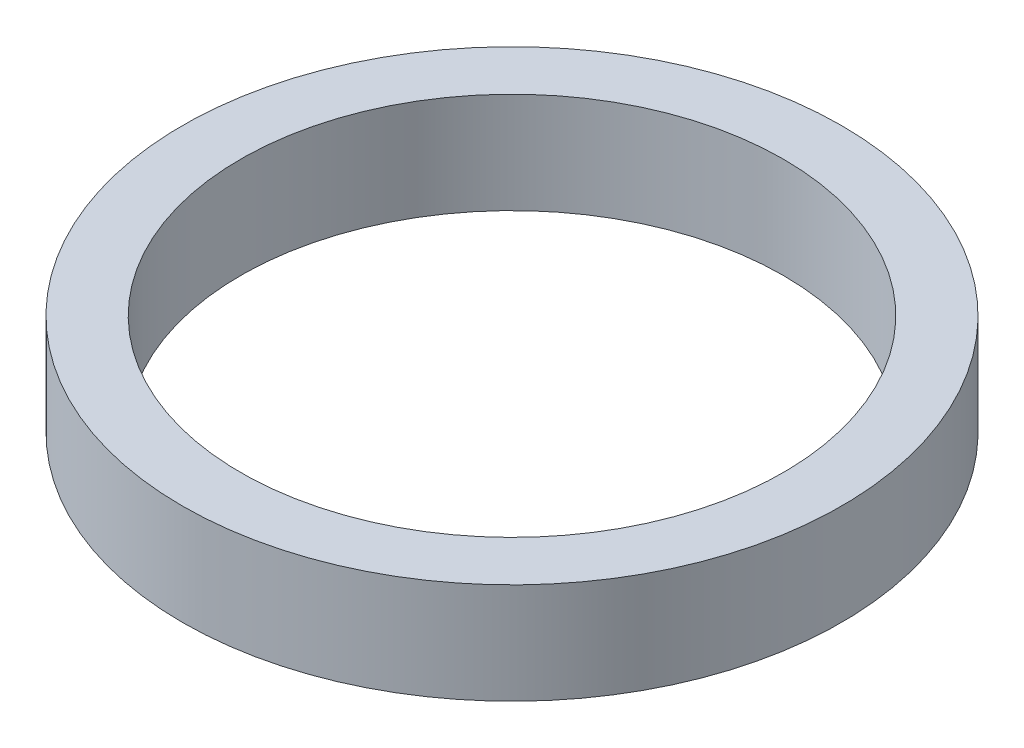
SolidWorks part; units mm, degrees
ref_plane "Front Plane" through (0, 0, 0) normal (0, 0, 1) x (1, 0, 0)
ref_plane "Top Plane" through (0, 0, 0) normal (0, 1, 0) x (1, 0, 0)
ref_plane "Right Plane" through (0, 0, 0) normal (1, 0, 0) x (0, 0, -1)
sketch "Sketch1" plane through (0, 0, 0) normal (0, 1, 0) x (1, 0, 0)
  circle A0 centre (0, 0) radius 42.5
  dimension "FLANGE_OD" = 85
extrude "Boss-Extrude1" add sketch "Sketch1" along normal blind 13
sketch "Sketch2" plane through (0, 0, 0) normal (0, 1, 0) x (1, 0, 0)
  circle A0 centre (0, 0) radius 35
  dimension "BORE_D" = 70
extrude "Cut-Extrude1" cut sketch "Sketch2" along normal through all
sketch "Sketch3" plane through (0, 13, 0) normal (0, 1, 0) x (1, 0, 0)
  circle A0 centre (0, 0) radius 19.6855 construction
  circle A1 centre (-19.6855, 0) radius 1.5
  dimension "BOLT_D" = 3
  dimension "BOLT_PCD" = 39.371
extrude "Cut-Extrude2" cut sketch "Sketch3" against normal blind 12.7837 rebuild error yes
pattern_circular "CirPattern1" count 4 over 360 rebuild error yes
